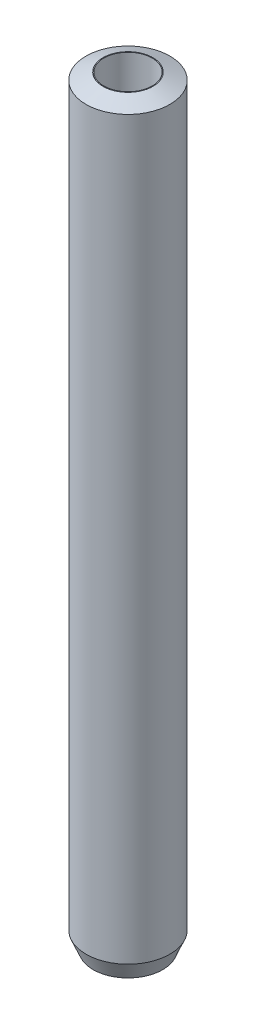
SolidWorks part; units mm, degrees
ref_plane "Front Plane" through (0, 0, 0) normal (0, 0, 1) x (1, 0, 0)
ref_plane "Top Plane" through (0, 0, 0) normal (0, 1, 0) x (1, 0, 0)
ref_plane "Right Plane" through (0, 0, 0) normal (1, 0, 0) x (0, 0, -1)
sketch "Sketch1" plane through (0, 0, 0) normal (0, 1, 0) x (1, 0, 0)
  circle A0 centre (0, 0) radius 30
  dimension "SHAFT_OD" = 60
extrude "Boss-Extrude1" add sketch "Sketch1" along normal blind 543.9771
sketch "Sketch2" plane through (0, 0, 0) normal (0, 1, 0) x (1, 0, 0)
  circle A0 centre (0, 0) radius 17.3155
  dimension "BORE_D" = 34.631
extrude "Cut-Extrude1" cut sketch "Sketch2" along normal through all
chamfer "Chamfer1" distance 5.0847 angle 67.274 2 edges at (0, 543.9771, 30) (0, 0, 30) first distance on face at (0, 543.9771, 30) first distance on face at (0, 0, 17.3155)
